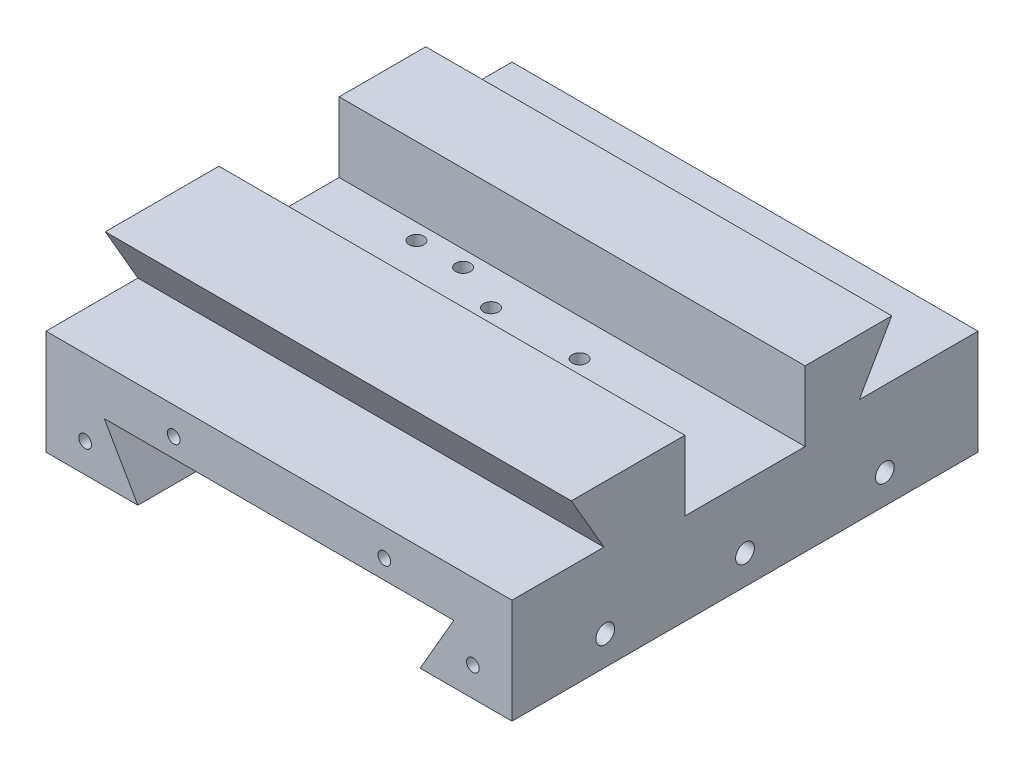
SolidWorks part; units mm, degrees
material "Ductile Iron"
ref_plane "Front Plane" through (0, 0, 0) normal (0, 0, 1) x (1, 0, 0)
ref_plane "Top Plane" through (0, 0, 0) normal (0, 1, 0) x (1, 0, 0)
ref_plane "Right Plane" through (0, 0, 0) normal (1, 0, 0) x (0, 0, -1)
sketch "Sketch10" plane through (0, 0, 0) normal (0, 0, 1) x (1, 0, 0)
  line B0 (-63.5, -15.875) -> (63.5, -15.875)
  line B1 (63.5, 0) -> (38.4596, 0)
  line B2 (38.4596, 0) -> (47.625, 15.875)
  line B3 (47.625, 15.875) -> (16.0563, 15.875)
  line B4 (-40.2927, 15.875) -> (-31.1272, 0)
  line B5 (-31.1272, 0) -> (-63.5, 0)
  line B6 (-63.5, 0) -> (-63.5, -15.875)
  line B7 (-38.4596, 0) -> (-47.625, 15.875)
  line B8 (-47.625, 15.875) -> (-40.2927, 15.875)
  line B9 (-16.0563, 15.875) -> (-16.0563, -3.175) construction
  line B10 (-16.0563, -3.175) -> (16.0563, -3.175) construction
  line B11 (16.0563, -3.175) -> (16.0563, 15.875) construction
  line B12 (-16.0563, 15.875) -> (-40.2927, 15.875)
  line B13 (-63.5, 0) -> (-63.5, 31.75)
  line B14 (-63.5, 31.75) -> (63.5, 31.75)
  line B15 (63.5, 31.75) -> (63.5, 0)
  line B16 (-16.0563, 15.875) -> (16.0563, 15.875) construction
  line B17 (0, 31.75) -> (0, -15.875) construction
  line B18 (-38.4596, 0) -> (38.4596, 0) construction
  line B19 (-28.702, 21.082) -> (28.702, 21.082) construction
  line B20 (-25.4, -8.001) -> (25.4, -8.001) construction
  line B21 (-25.4, -8.001) -> (-25.4, 7.9375) construction
  line B22 (25.4, -8.001) -> (25.4, 7.9375) construction
  line B23 (-52.832, 7.9375) -> (52.832, 7.9375) construction
  circle B24 centre (0, 6.35) radius 18.669 construction
  line B25 (40.2927, 15.875) -> (31.1272, 0)
  line B26 (31.1272, 0) -> (38.4596, 0)
  line B27 (-15.875, 15.875) -> (-15.875, -3.175)
  line B28 (-16.0563, 15.875) -> (-15.875, 15.875)
  line B29 (-15.875, -3.175) -> (15.875, -3.175)
sketch_block_instance "dovetail pair-1"
sketch_block "dovetail pair" parameters "D8"=37.338, "D1"=60, "D2"=127, "D3"=6.35, "D4"=15.875, "D5"=31.75, "D6"=95.25, "D7"=19.05, "D9"=60, "D10"=31.75, "D11"=50.8, "D12"=23.876, "D13"=7.874, "D14"=10.668, "D15"=34.798, "D16"=21.082, "D17"=7.9375, "D18"=24.4437
sketch "Sketch11"
sketch_block_instance "dovetail pair-3"
sketch "female-dovetail-profile" plane through (0, 0, 0) normal (0, 0, 1) x (1, 0, 0)
  line L0 (-47.625, 15.875) -> (-40.2927, 15.875) construction
  line L1 (-16.0563, 15.875) -> (-40.2927, 15.875) construction
  line L2 (-16.0563, 15.875) -> (16.0563, 15.875) construction
  line L3 (47.625, 15.875) -> (16.0563, 15.875) construction
  line L4 (-47.625, 15.875) -> (-40.2927, 15.875)
  line L5 (-16.0563, 15.875) -> (-40.2927, 15.875)
  line L6 (-16.0563, 15.875) -> (16.0563, 15.875)
  line L7 (47.625, 15.875) -> (16.0563, 15.875)
  line L8 (-38.4596, 0) -> (-47.625, 15.875) construction
  line L9 (-63.5, 0) -> (-63.5, 31.75) construction
  line L10 (63.5, 31.75) -> (63.5, 0) construction
  line L11 (63.5, 0) -> (38.4596, 0) construction
  line L12 (38.4596, 0) -> (47.625, 15.875) construction
  line L13 (-38.4596, 0) -> (-47.625, 15.875)
  line L14 (-63.5, 0) -> (-63.5, 31.75)
  line L15 (63.5, 31.75) -> (63.5, 0)
  line L16 (63.5, 0) -> (38.4596, 0)
  line L17 (38.4596, 0) -> (47.625, 15.875)
  line L18 (-38.4596, 0) -> (-63.5, 0)
  line L20 (63.5, 31.75) -> (63.5, 44.45)
  line L21 (63.5, 44.45) -> (-63.5, 44.45)
  line L22 (-63.5, 44.45) -> (-63.5, 31.75)
  dimension "D1" = 44.45
extrude "x-carriage-extrude" add sketch "female-dovetail-profile" along normal mid plane 127
sketch "male-dovetail-shoulder-profile" plane through (0, 0, 0) normal (1, 0, 0) x (0, 0, -1)
  line L0 (40.2927, 44.45) -> (31.1272, 28.575) construction
  line L1 (-40.2927, 44.45) -> (-31.1272, 28.575) construction
  line L2 (38.4596, 28.575) -> (47.625, 44.45) construction
  line L3 (63.5, 28.575) -> (38.4596, 28.575) construction
  line L4 (-38.4596, 28.575) -> (-47.625, 44.45) construction
  line L5 (-40.2927, 44.45) -> (-31.1272, 28.575) construction
  line L6 (38.4596, 28.575) -> (47.625, 44.45) construction
  line L7 (63.5, 28.575) -> (38.4596, 28.575)
  line L8 (-16.0563, 44.45) -> (-16.0563, 25.4) construction
  line L9 (-16.0563, 25.4) -> (16.0563, 25.4) construction
  line L10 (16.0563, 25.4) -> (16.0563, 44.45) construction
  line L11 (47.625, 44.45) -> (16.0563, 44.45) construction
  line L12 (-47.3317, 43.942) -> (-38.4596, 28.575)
  line L14 (-16.0563, 44.45) -> (-16.0563, 25.4) construction
  line L15 (-16.0563, 25.4) -> (16.0563, 25.4) construction
  line L16 (16.0563, 25.4) -> (16.0563, 44.45) construction
  line L17 (47.625, 44.45) -> (16.0563, 44.45) construction
  line L18 (-38.4596, 28.575) -> (-63.5, 28.575)
  line L19 (-16.0563, 44.45) -> (-40.2927, 44.45) construction
  line L20 (-47.3317, 43.942) -> (-16.383, 43.942)
  line L21 (-16.383, 43.942) -> (-16.383, 24.892)
  line L22 (-16.383, 24.892) -> (16.383, 24.892)
  line L23 (16.383, 24.892) -> (16.383, 43.942)
  line L24 (16.383, 43.942) -> (39.9994, 43.942)
  line L25 (39.9994, 43.942) -> (31.1272, 28.575)
  line L26 (-63.5, 28.575) -> (-63.5, 44.45)
  line L27 (-63.5, 44.45) -> (63.5, 44.45)
  line L28 (63.5, 44.45) -> (63.5, 28.575)
  line L29 (0, 60.325) -> (0, 12.7) construction
  line L30 (-31.1272, 28.575) -> (-63.5, 28.575) construction
  line L31 (31.1272, 28.575) -> (38.4596, 28.575)
  line L32 (-15.875, 44.45) -> (-15.875, 25.4) construction
  line L33 (-63.5, 28.575) -> (-63.5, 60.325) construction
  line L34 (-16.0563, 44.45) -> (16.0563, 44.45) construction
  line L35 (-38.4596, 28.575) -> (38.4596, 28.575) construction
  point P16 (0, 24.892)
  dimension "D2" = 0.508
  dimension "D3" = 0.508
  dimension "D1" = 0.508
extrude "y-guide-cut-extrude" cut sketch "male-dovetail-shoulder-profile" against normal mid plane 127
hole_wizard "#8-32 Tapped Hole1" positions "Sketch4" profile "Sketch5" tap size "#8-32" standard "ANSI Inch"
sketch "Sketch4" plane through (0, -15.875, 63.5) normal (0, 0, 1) x (1, 0, 0)
  point P32 (-52.832, 23.8125)
  point P34 (-28.702, 36.957)
  point P36 (28.702, 36.957)
  point P38 (52.832, 23.8125)
cosmetic thread "Hole Thread12" parameters "D1"=8.382, "D2"=4.1656
sketch "Sketch5" plane through (-52.832, 7.9375, 63.5) normal (1, 0, 0) x (0, -1, 0)
  line L0 (0, 0) -> (0, 13.3822)
  line L1 (0, 13.3822) -> (1.7272, 12.3444)
  line L2 (1.7272, 12.3444) -> (1.7272, 0)
  line L3 (1.7272, 0) -> (0, 0)
  line L4 (0, 13.3822) -> (-1.7272, 12.3444) construction
  line L5 (0, -6.35) -> (0, 107.95) construction
  dimension "Tap Drill Dia." = 3.4544
  dimension "Tap Drill Depth" = 12.3444
  dimension "Drill Angle" = 118
cosmetic thread "Hole Thread20" parameters "D1"=8.382, "D2"=4.1656
cosmetic thread "Hole Thread21" parameters "D1"=8.382, "D2"=4.1656
cosmetic thread "Hole Thread22" parameters "D1"=8.382, "D2"=4.1656
hole_wizard "#8-32 Tapped Hole2" positions "Sketch6" profile "Sketch7" tap size "#8-32" standard "ANSI Inch"
sketch "Sketch6" plane through (0, -15.875, -63.5) normal (0, 0, -1) x (-1, 0, 0)
  point P8 (-52.832, 23.8125)
  point P10 (-28.702, 36.957)
  point P12 (28.702, 36.957)
  point P14 (52.832, 23.8125)
cosmetic thread "Hole Thread15" parameters "D1"=8.382, "D2"=4.1656
sketch "Sketch7" plane through (52.832, 7.9375, -63.5) normal (1, 0, 0) x (0, 1, 0)
  line L0 (0, 0) -> (0, 13.4838)
  line L1 (0, 13.4838) -> (1.7272, 12.446)
  line L2 (1.7272, 12.446) -> (1.7272, 0)
  line L5 (1.7272, 0) -> (0, 0)
  line L10 (0, 13.4838) -> (-1.7272, 12.446) construction
  line L11 (0, -6.35) -> (0, 107.95) construction
  dimension "Tap Drill Dia." = 3.4544
  dimension "Tap Drill Depth" = 12.446
  dimension "Drill Angle" = 118
cosmetic thread "Hole Thread23" parameters "D1"=8.382, "D2"=4.1656
cosmetic thread "Hole Thread24" parameters "D1"=8.382, "D2"=4.1656
cosmetic thread "Hole Thread25" parameters "D1"=8.382, "D2"=4.1656
hole_wizard "gib screw 1/4-20 Tapped Hole1" positions "Sketch9" profile "Sketch8" tap size "1/4-20" standard "ANSI Inch" end condition up to next
sketch "Sketch9" plane through (0, 0, 0) normal (1, 0, 0) x (0, 0, -1)
  line L2 (0, 15.875) -> (0, 0) construction
  line L4 (63.5, 7.9375) -> (-63.5, 7.9375) construction
  line L7 (-38.1, 7.9375) -> (0, 7.9375) construction
  line L8 (63.5, 0) -> (63.5, 28.575) construction
  line L9 (-63.5, 15.875) -> (63.5, 15.875) construction
  line L10 (-63.5, 15.875) -> (63.5, 15.875)
  point P0 (-38.1, 7.9375)
  point P16 (0, 7.9375)
  point P22 (0, 7.9375)
  point P23 (38.1, 7.9375)
  dimension "D1" = 38.1
  dimension "D2" = 3
sketch "Sketch8" plane through (0, 7.9375, 38.1) normal (0, 1, 0) x (0, 0, 1)
  line L0 (0, 0) -> (0, 63.5)
  line L1 (0, 63.5) -> (2.5527, 63.5)
  line L2 (2.5527, 63.5) -> (2.5527, 0)
  line L5 (2.5527, 0) -> (0, 0)
  line L11 (0, -6.35) -> (0, 107.95) construction
  dimension "Thru Tap Drill Dia." = 5.1054
  dimension "Thru Tap Drill Depth" = 63.5
cosmetic thread "Hole Thread36" parameters "D1"=23.2203, "D2"=6.35
cosmetic thread "Hole Thread37" parameters "D1"=23.2203, "D2"=6.35
cosmetic thread "Hole Thread38" parameters "D1"=23.2203, "D2"=6.35
hole_wizard "#10-32 Tapped Hole1" positions "Sketch13" profile "Sketch12" tap size "#10-32" standard "ANSI Inch" end condition up to next
sketch "Sketch13" plane through (0, 24.892, 0) normal (0, 1, 0) x (1, 0, 0)
  line L1 (-12.065, -6.35) -> (12.065, -6.35) construction
  line L2 (-12.065, -6.35) -> (-12.065, 6.35) construction
  line L3 (-12.065, 6.35) -> (12.065, 6.35) construction
  line L4 (12.065, -6.35) -> (12.065, 6.35) construction
  line L6 (-38.1, -12.065) -> (-25.4, -12.065) construction
  line L7 (-38.1, -12.065) -> (-38.1, 12.065) construction
  line L8 (-38.1, 12.065) -> (-25.4, 12.065) construction
  line L9 (-25.4, -12.065) -> (-25.4, 12.065) construction
  line L10 (0, 16.383) -> (0, -16.383) construction
  line L12 (-63.5, -16.383) -> (63.5, -16.383) construction
  line L13 (-63.5, 0) -> (63.5, 0) construction
  line L14 (-63.5, -16.383) -> (-63.5, 16.383) construction
  line L15 (63.5, -16.383) -> (63.5, 16.383) construction
  line L16 (-63.5, 16.383) -> (63.5, 16.383) construction
  point P0 (-38.1, 12.065)
  point P2 (-38.1, -12.065)
  point P4 (-12.065, 6.35)
  point P6 (-25.4, 12.065)
  point P8 (-25.4, -12.065)
  point P10 (12.065, 6.35)
  point P12 (12.065, -6.35)
  point P14 (-12.065, -6.35)
  point P155 (0, 0)
  point P157 (0, -6.35)
  point P158 (12.065, 0)
  point P159 (-25.4, 0)
  dimension "D1" = 24.13
  dimension "D2" = 24.13
  dimension "D3" = 12.7
  dimension "D4" = 12.7
  dimension "D5" = 38.1
sketch "Sketch12" plane through (-38.1, 24.892, -12.065) normal (1, 0, 0) x (0, 0, 1)
  line L0 (0, 0) -> (0, 9.017)
  line L1 (0, 9.017) -> (2.0193, 9.017)
  line L2 (2.0193, 9.017) -> (2.0193, 0)
  line L5 (2.0193, 0) -> (0, 0)
  line L11 (0, -6.35) -> (0, 107.95) construction
  dimension "Thru Tap Drill Dia." = 4.0386
  dimension "Thru Tap Drill Depth" = 9.017
cosmetic thread "Hole Thread28" parameters "D2"=4.826
cosmetic thread "Hole Thread29" parameters "D2"=4.826
cosmetic thread "Hole Thread30" parameters "D2"=4.826
cosmetic thread "Hole Thread31" parameters "D2"=4.826
cosmetic thread "Hole Thread32" parameters "D2"=4.826
cosmetic thread "Hole Thread33" parameters "D2"=4.826
cosmetic thread "Hole Thread34" parameters "D2"=4.826
cosmetic thread "Hole Thread35" parameters "D2"=4.826
equation "\"dovetail-angle\"= 60"
equation "\"dovetail-stock-width\"= 5"
equation "\"dovetail-stock-height\"= 1.25"
equation "\"dovetail-depth\"= 0.5 * \"dovetail-stock-height\""
equation "\"dovetail-throat-width\"= \"dovetail-stock-width\" - (2 * \"dovetail-depth\")"
equation "\"delta-x\"= 6"
equation "\"delta-y\"= 3"
equation "\"delta-z\"= 2.5"
equation "\"gib-thickness\"= 0.25"
equation "\"x-slide-length\"= \"dovetail-stock-width\" + \"delta-x\""
equation "\"y-slide-length\"= \"dovetail-stock-width\" + \"delta-y\""
equation "\"dog-point-diam\"= .149"
equation "\"D1@female-dovetail-profile\"=\"dovetail-double-height\""
equation "\"D1@x-carriage-extrude\"=\"dovetail-stock-width\""
equation "\"dog-point-length\"= .067"
equation "\"dovetail-double-height\"= 2 * \"dovetail-depth\" + 0.5"
equation "\"D2@male-dovetail-shoulder-profile\"=\"acme_nut_clearance\""
equation "\"D3@male-dovetail-shoulder-profile\"=\"dovetail_male_clearance\""
equation "\"acme-major-diam\"= .5"
equation "\"acme-pitch-diam\"= 0.45"
equation "\"acme-minor-diam\"= 0.4"
equation "\"acme-nut-od\"= 1.47"
equation "\"acme-nut-length\"= 1"
equation "\"acme-nut-trim-height\"= .75"
equation "\"screw-bearing-od\"= 0.5"
equation "\"screw-bearing-length\"= .375"
equation "\"screw-bearing-id\"= .3125"
equation "\"end-plate-thickness\"= \"screw-bearing-length\""
equation "\"screw-add-length\"= 2 * \"end-plate-thickness\" + 1 + 0.5"
equation "\"x-screw-length\"= \"x-slide-length\" + \"screw-add-length\""
equation "\"y-screw-length\"= \"y-slide-length\" + \"screw-add-length\""
equation "\"acme-nut-mount-hole-space-horz\"= 0.95"
equation "\"acme-nut-mount-hole-space-vert\"= 0.5 * \"acme-nut-length\""
equation "\"D2@dovetail pair\"=\"dovetail-stock-width\""
equation "\"D1@dovetail pair\"=\"dovetail-angle\""
equation "\"D3@dovetail pair\"=\"gib-thickness\""
equation "\"D4@dovetail pair\"=\"dovetail-depth\""
equation "\"D5@dovetail pair\"=\"dovetail-stock-height\""
equation "\"D6@dovetail pair\"=\"dovetail-throat-width\""
equation "\"D10@dovetail pair\"=\"dovetail-stock-height\""
equation "\"D7@dovetail pair\"=\"acme-nut-trim-height\""
equation "\"D8@dovetail pair\"=\"acme-nut-od\""
equation "\"D9@dovetail pair\"=\"dovetail-angle\""
equation "\"D17@dovetail pair\"=\"dovetail-depth\"/2"
equation "\"acme-nut-trim-width\"= 1.25"
equation "\"vise-hole-center-dist\"= 6.75"
equation "\"wiper_plate_clearance\"= .03"
equation "\"dial-width\"= 0.5"
equation "\"quarter-twenty-free-fit\"= .2667"
equation "\"acme_nut_clearance\"= .02"
equation "\"dovetail_male_clearance\"= .02"
equation "\"D1@y-guide-cut-extrude\"=\"dovetail-stock-width\""
equation "\"D1@male-dovetail-shoulder-profile\"=\"acme_nut_clearance\""
equation "\"D1@Sketch13\"=\"acme-nut-mount-hole-space-horz\""
equation "\"D2@Sketch13\"=\"acme-nut-mount-hole-space-horz\""
equation "\"D3@Sketch13\"=\"acme-nut-mount-hole-space-vert\""
equation "\"D4@Sketch13\"=\"acme-nut-mount-hole-space-vert\""
